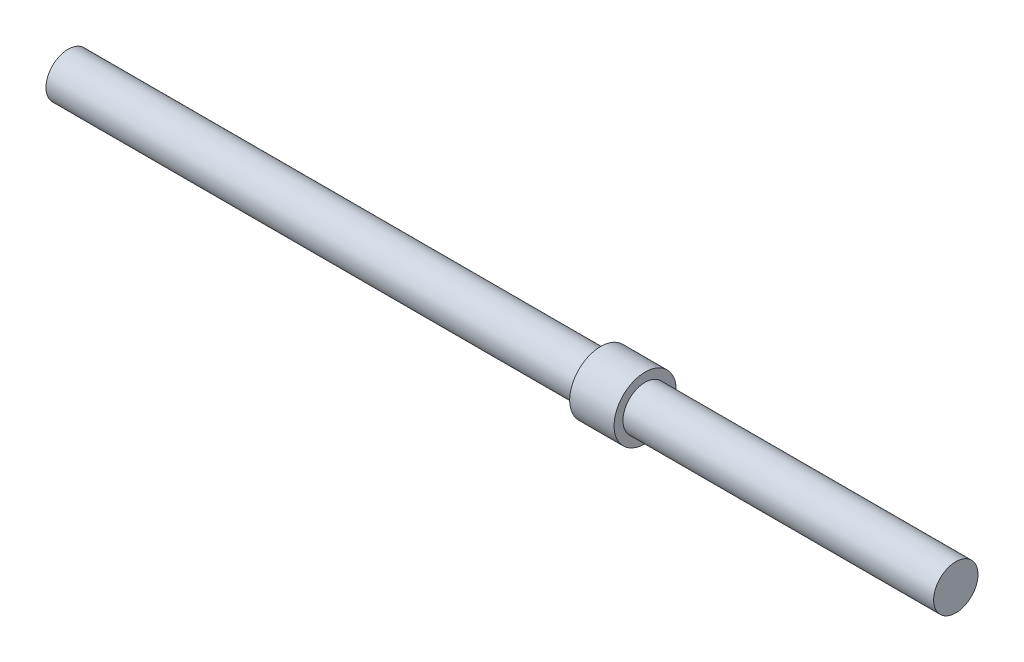
SolidWorks part; units mm, degrees
ref_plane "Front Plane" through (0, 0, 0) normal (0, 0, 1) x (1, 0, 0)
ref_plane "Top Plane" through (0, 0, 0) normal (0, 1, 0) x (1, 0, 0)
ref_plane "Right Plane" through (0, 0, 0) normal (1, 0, 0) x (0, 0, -1)
sketch "Sketch1" plane through (0, 0, 0) normal (1, 0, 0) x (0, 0, -1)
  circle A0 centre (0, 0) radius 5
  dimension "D1" = 10
extrude "Boss-Extrude1" add sketch "Sketch1" along normal mid plane 200
sketch "Sketch2" plane through (100, 0, 0) normal (1, 0, 0) x (0, 0, -1)
  circle A0 centre (0, 0) radius 7
  dimension "D1" = 14
extrude "Boss-Extrude2" add sketch "Sketch2" against normal blind 10 from offset 70 offset against normal yes
